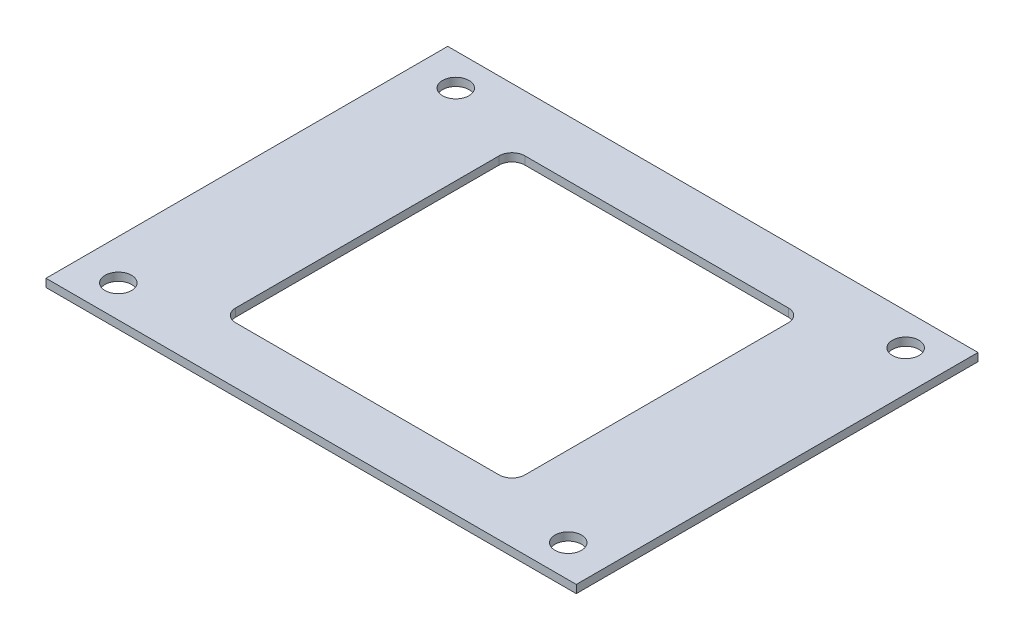
SolidWorks part; units mm, degrees
ref_plane "Front Plane" through (0, 0, 0) normal (0, 0, 1) x (1, 0, 0)
ref_plane "Top Plane" through (0, 0, 0) normal (0, 1, 0) x (1, 0, 0)
ref_plane "Right Plane" through (0, 0, 0) normal (1, 0, 0) x (0, 0, -1)
sketch "Sketch1" plane through (0, 0, 0) normal (0, 1, 0) x (1, 0, 0)
  line L1 (-33, -25) -> (33, -25)
  line L2 (-33, -25) -> (-33, 25)
  line L3 (-33, 25) -> (33, 25)
  line L4 (33, -25) -> (33, 25)
  line L5 (-33, -25) -> (33, 25) construction
  line L6 (-33, 25) -> (33, -25) construction
  line L7 (-18, -18) -> (18, -18)
  line L8 (-18, -18) -> (-18, 18)
  line L9 (-18, 18) -> (18, 18)
  line L10 (18, -18) -> (18, 18)
  line L11 (-18, -18) -> (18, 18) construction
  line L12 (-18, 18) -> (18, -18) construction
  circle A0 centre (-28, 21) radius 1.65
  circle A1 centre (-28, -21) radius 1.65
  circle A2 centre (28, 21) radius 1.65
  circle A3 centre (28, -21) radius 1.65
  point P0 (0, 0)
  point P5 (0, 0)
  dimension "D5" = 3
  dimension "D6" = 3
  dimension "D7" = 10
  dimension "D8" = 10
  dimension "D9" = 3.3
  dimension "D10" = 3.3
  dimension "D11" = 3
  dimension "D12" = 3
  dimension "D13" = 10
  dimension "D15" = 3.3
  dimension "D16" = 3.3
  dimension "D1" = 66
  dimension "D2" = 50
  dimension "D3" = 36
  dimension "D4" = 36
  dimension "D14" = 10
extrude "Boss-Extrude1" add sketch "Sketch1" along normal blind 1
fillet "Fillet1" radius 1.6 4 edges at (-18, 0.5, 18) (18, 0.5, 18) (18, 0.5, -18) (-18, 0.5, -18)
